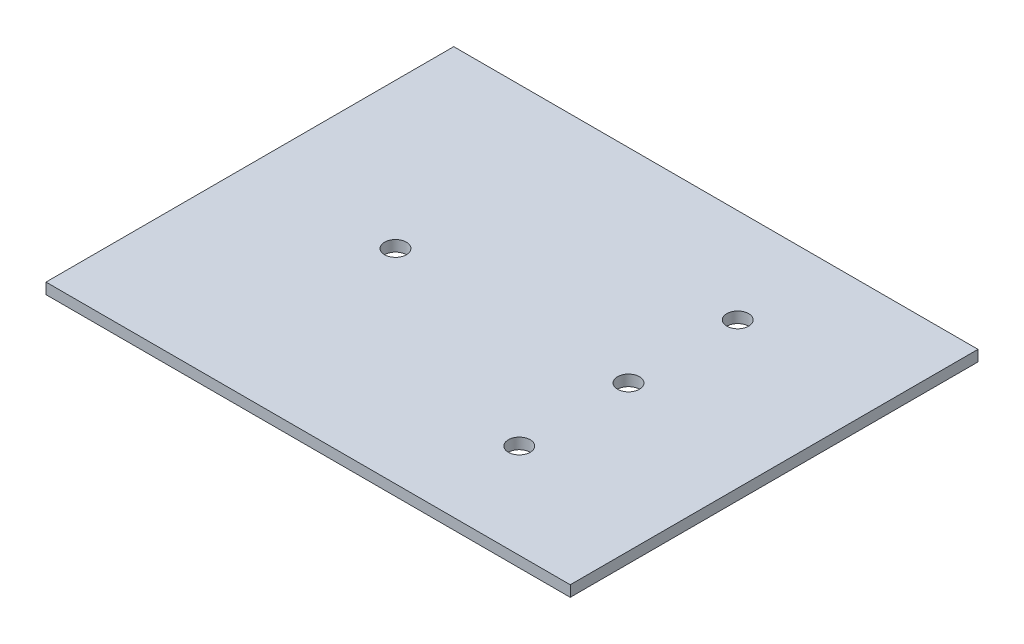
SolidWorks part; units mm, degrees
material "Oak"
ref_plane "Front Plane" through (0, 0, 0) normal (0, 0, 1) x (1, 0, 0)
ref_plane "Top Plane" through (0, 0, 0) normal (0, 1, 0) x (1, 0, 0)
ref_plane "Right Plane" through (0, 0, 0) normal (1, 0, 0) x (0, 0, -1)
sketch "Sketch1" plane through (0, 0, 0) normal (0, 1, 0) x (1, 0, 0)
  line L0 (558.8, 99.2707) -> (461.5124, 17.6367)
  line L1 (-558.8, -177.8) -> (558.8, -177.8)
  line L2 (-558.8, 177.8) -> (558.8, 177.8)
  line L3 (558.8, -177.8) -> (558.8, 177.8)
  line L4 (-558.8, -177.8) -> (558.8, 177.8) construction
  line L5 (-558.8, 177.8) -> (558.8, -177.8) construction
  line L6 (-228.6, 177.8) -> (228.6, 177.8)
  line L7 (-228.6, -177.8) -> (228.6, -177.8)
  line L8 (228.6, 177.8) -> (228.6, -177.8)
  line L9 (-228.6, 177.8) -> (228.6, -177.8) construction
  line L10 (-228.6, -177.8) -> (228.6, 177.8) construction
  line L11 (228.6, -177.8) -> (558.8, 99.2707)
  line L12 (-228.6, 177.8) -> (-228.6, -177.8)
  point P4 (0, 0)
extrude "Boss-Extrude1" add sketch "Sketch1" along normal blind 9.525 contours L8 L11 L0 L3 L2 region at (358.5765, 0, -54.5316)
extrude "Boss-Extrude2" add sketch "Sketch1<4>" along normal blind 9.525 contours L11 L1 L3 L0 region at (448.7333, 0, 85.4431)
sketch "Sketch1<4>" plane through (0, 0, 0) normal (0, 1, 0) x (1, 0, 0) same geometry as "Sketch1"
sketch "Sketch4" plane through (0, 0, 0) normal (0, -1, 0) x (1, 0, 0)
  line L1 (558.8, 177.8) -> (622.3, 177.8)
  line L2 (558.8, 177.8) -> (558.8, -177.8)
  line L3 (558.8, -177.8) -> (622.3, -177.8)
  line L4 (228.6, 177.8) -> (228.6, -177.8)
  line L5 (228.6, -177.8) -> (558.8, -177.8)
  line L6 (558.8, -177.8) -> (558.8, 177.8)
  line L7 (558.8, 177.8) -> (228.6, 177.8)
  line L8 (228.6, 177.8) -> (228.6, -177.8)
  line L9 (228.6, -177.8) -> (558.8, -177.8)
  line L10 (558.8, -177.8) -> (558.8, 177.8)
  line L11 (558.8, 177.8) -> (228.6, 177.8)
  line L12 (622.3, 177.8) -> (622.3, -177.8)
  line L13 (228.6, 177.8) -> (165.1, 177.8)
  line L14 (228.6, 177.8) -> (228.6, -177.8)
  line L15 (228.6, -177.8) -> (165.1, -177.8)
  line L16 (165.1, 177.8) -> (165.1, -177.8)
  line M9 (228.6, 177.8) -> (228.6, -177.8)
  line M11 (558.8, -177.8) -> (558.8, 177.8)
  dimension "D1" = 0
extrude "Boss-Extrude3" add sketch "Sketch4" against normal blind 9.525 contours L13 L16 L15 M9 | L12 L1 L3 M11 region at (590.55, 0, 0) region at (196.85, 0, 0)
sketch "Sketch5" plane through (0, 0, 0) normal (0, -1, 0) x (1, 0, 0)
  line L0 (393.7, -177.8) -> (393.7, 177.8)
  line L1 (165.1, 0) -> (622.3, 0)
  line L2 (495.3, 0) -> (495.3, 95.25)
  line L3 (495.3, 0) -> (495.3, -95.25)
  line L4 (622.3, 177.8) -> (165.1, 177.8)
  line L5 (165.1, 177.8) -> (165.1, -177.8)
  line L6 (165.1, -177.8) -> (622.3, -177.8)
  line L7 (622.3, -177.8) -> (622.3, 177.8)
  line L8 (622.3, 177.8) -> (165.1, 177.8)
  line L9 (165.1, 177.8) -> (165.1, -177.8)
  line L10 (165.1, -177.8) -> (622.3, -177.8)
  line L11 (622.3, -177.8) -> (622.3, 177.8)
  circle A0 centre (495.3, 0) radius 9.525
  circle A1 centre (292.1, 0) radius 9.525
  circle A2 centre (495.3, -95.25) radius 9.525
  circle A3 centre (495.3, 95.25) radius 9.525
  dimension "D2" = 101.6
  dimension "D3" = 203.2
  dimension "D1" = 0
extrude "Cut-Extrude1" cut sketch "Sketch5" against normal through all contours L1 A1 | L1 A1 | A2 | L2 A0 L1 | L1 A0 L2 | L3 A0 L1 | L1 A0 L3 | A3 region at (501.8447, 0, -88.7053) region at (488.7553, 0, 101.7947) region at (292.1, 0, -4.0425) region at (292.1, 0, 4.0425) region at (491.2575, 0, 4.0425) region at (491.2575, 0, -4.0425) region at (499.3425, 0, 4.0425) region at (499.3425, 0, -4.0425)
